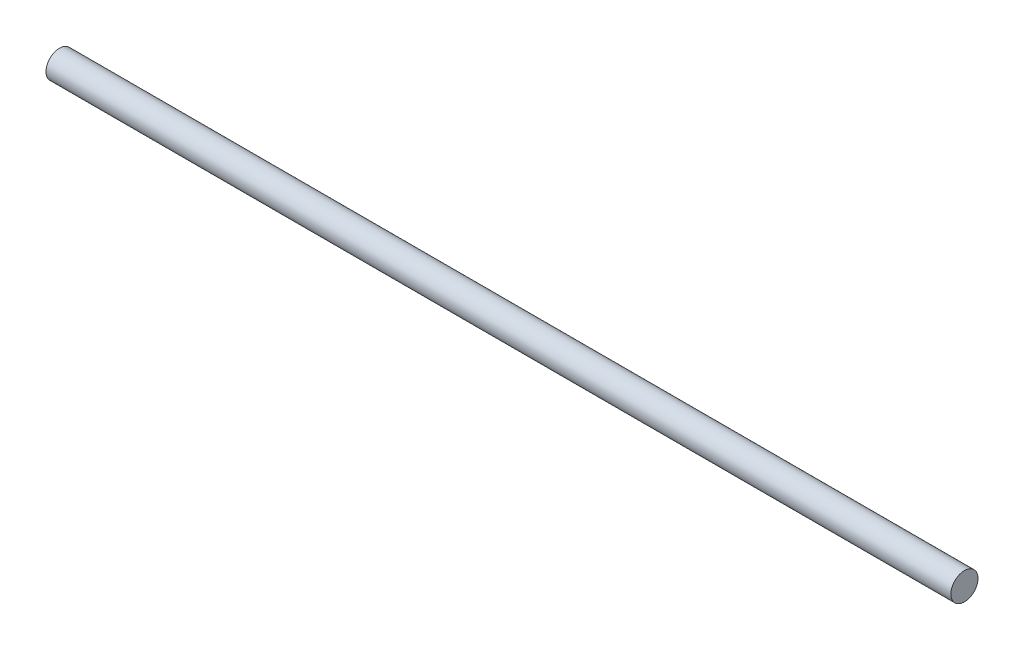
SolidWorks part; units mm, degrees
ref_plane "Front Plane" through (0, 0, 0) normal (0, 0, 1) x (1, 0, 0)
ref_plane "Top Plane" through (0, 0, 0) normal (0, 1, 0) x (1, 0, 0)
ref_plane "Right Plane" through (0, 0, 0) normal (1, 0, 0) x (0, 0, -1)
other "Configuration Table"
sketch "草图1" plane through (0, 0, 0) normal (1, 0, 0) x (0, 0, -1)
  circle A0 centre (0, 0) radius 1.5
  dimension "D1" = 3
extrude "凸台-拉伸1" add sketch "草图1" along normal blind 100
